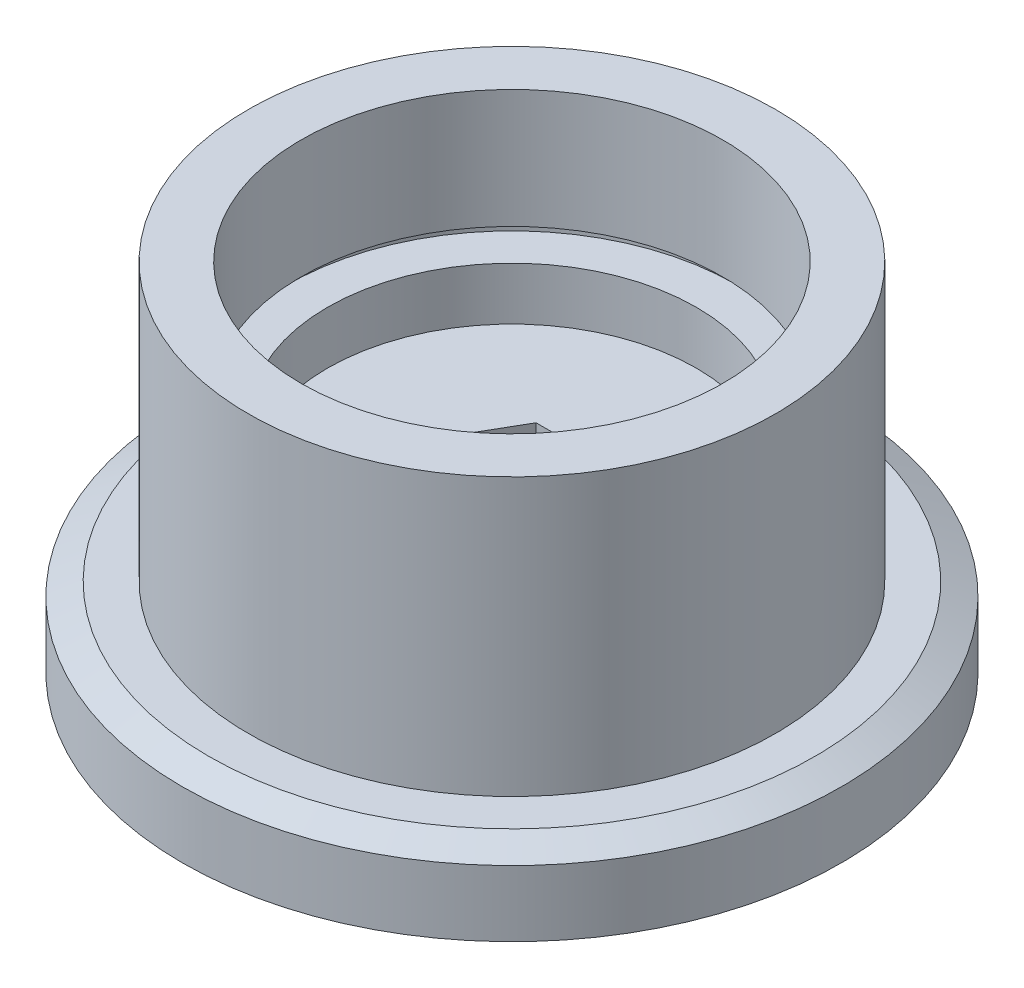
SolidWorks part; units mm, degrees
material "Cuivre"
ref_plane "Plan de face" through (0, 0, 0) normal (0, 0, 1) x (1, 0, 0)
ref_plane "Plan de dessus" through (0, 0, 0) normal (0, 1, 0) x (1, 0, 0)
ref_plane "Plan de droite" through (0, 0, 0) normal (1, 0, 0) x (0, 0, -1)
sketch "Esquisse1" plane through (0, 0, 0) normal (0, 1, 0) x (1, 0, 0)
  circle A0 centre (0, 0) radius 12.5
  point P3 (0, 0)
  dimension "D1" = 25
extrude "Boss.-Extru.1" add sketch "Esquisse1" along normal blind 3.5
cosmetic thread "Représentation de filetage2" parameters "D2"=23.5
sketch "Esquisse2" plane through (0, 3.5, 0) normal (0, 1, 0) x (1, 0, 0)
  circle A0 centre (0, 0) radius 10
  dimension "D1" = 20
extrude "Boss.-Extru.2" add sketch "Esquisse2" along normal blind 10.5
sketch "Esquisse6" plane through (0, 14, 0) normal (0, 1, 0) x (1, 0, 0)
  circle A0 centre (0, 0) radius 8
  dimension "D1" = 16
extrude "Enlèv. mat.-Extru.1" cut sketch "Esquisse6" against normal blind 4.5
sketch "Esquisse5" plane through (0, 9.5, 0) normal (0, -1, 0) x (1, 0, 0)
  circle A0 centre (0, 0) radius 8.5
  dimension "D1" = 17
extrude "Enlèv. mat.-Extru.3" cut sketch "Esquisse5" along normal blind 0.5
sketch "Esquisse4" plane through (0, 9, 0) normal (0, -1, 0) x (1, 0, 0)
  circle A0 centre (0, 0) radius 7
  dimension "D1" = 14
extrude "Enlèv. mat.-Extru.2" cut sketch "Esquisse4" along normal blind 2
chamfer "Chanfrein1" distance 0.5 distance2 1 1 edges at (0, 3.5, 12.5) first distance on face at (0, 3.5, 12.5)
chamfer "Chanfrein2" distance 1 distance2 0.5 1 edges at (0, 0, 12.5) first distance on face at (0, 0, 12.5)
sketch "Sketch1" plane through (0, 0, 0) normal (0, -1, 0) x (1, 0, 0)
  line L7 (2.5, 0) -> (1.25, 2.1651)
  line L8 (1.25, 2.1651) -> (-1.25, 2.1651)
  line L9 (-1.25, 2.1651) -> (-2.5, 0)
  line L10 (-2.5, 0) -> (-1.25, -2.1651)
  line L11 (-1.25, -2.1651) -> (1.25, -2.1651)
  line L12 (1.25, -2.1651) -> (2.5, 0)
  circle A0 centre (0, 0) radius 2.1651 construction
  dimension "D2" = 2.5
  dimension "D1" = 2.1651
extrude "Cut-Extrude1" cut sketch "Sketch1" against normal blind 7
